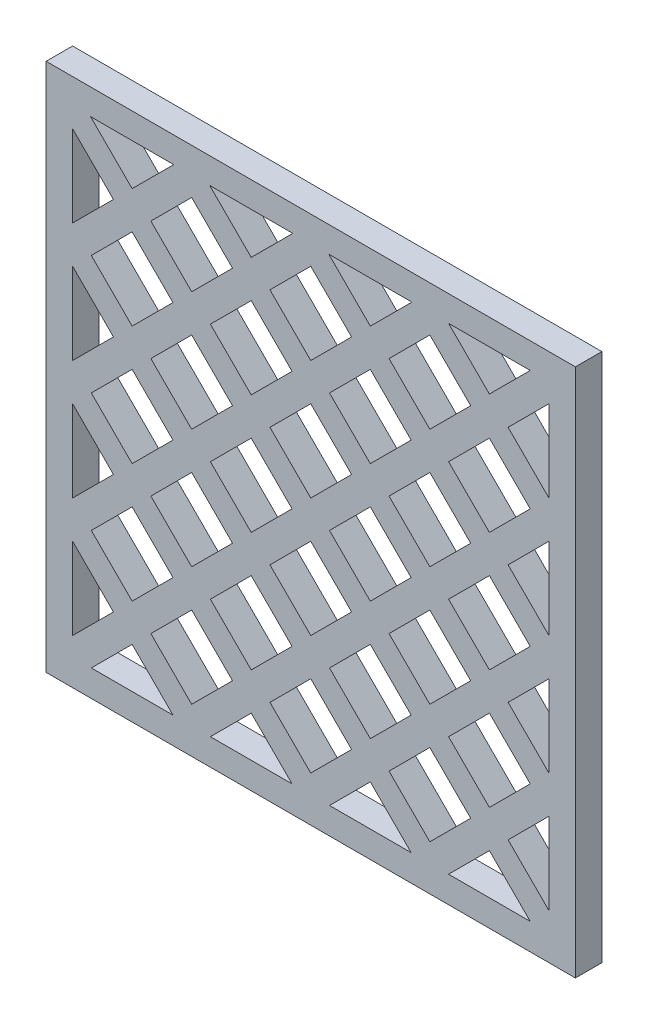
SolidWorks part; units mm, degrees
ref_plane "Front Plane" through (0, 0, 0) normal (0, 0, 1) x (1, 0, 0)
ref_plane "Top Plane" through (0, 0, 0) normal (0, 1, 0) x (1, 0, 0)
ref_plane "Right Plane" through (0, 0, 0) normal (1, 0, 0) x (0, 0, -1)
sketch "Sketch4" plane through (0, 0, 0) normal (0, 0, 1) x (1, 0, 0)
  line L0 (-16.7778, -18) -> (-10.4142, -18) construction
  line L1 (-16.6426, 18.0568) -> (-10.3574, 18.0568)
  line L2 (-18, 16.5858) -> (-18, 10.4142)
  line L3 (-16.7778, -18) -> (-10.4142, -18)
  line L5 (10.4142, -18) -> (16.5858, -18)
  line L6 (-18, -18) -> (0, 0) construction
  line L7 (-9, -18) -> (-9, -9) construction
  line L8 (-9, -9) -> (-18, -9) construction
  line L9 (-18, -10.4142) -> (-18, -16.7778) construction
  line L12 (-10.4142, -9) -> (-13.5, -12.0858)
  line L15 (-9, -10.4142) -> (-12.0858, -13.5)
  line L16 (-10.2222, -9) -> (-16.7778, -18) construction
  line L17 (-18, -16.7778) -> (-9, -10.2222) construction
  line L22 (-13.5, -13.5) -> (-13.5, -18) construction
  line L23 (-13.5, -18) -> (-13.5, -9) construction
  line L24 (-9, -13.5) -> (-18, -13.5) construction
  line L25 (-18, -13.5) -> (-13.5, -13.5) construction
  line L26 (-14.9142, -13.5) -> (-18, -16.5858)
  line L27 (-13.5, -14.9142) -> (-16.5858, -18)
  line L28 (-9, -16.5858) -> (-12.0858, -13.5)
  line L29 (-13.5, -14.9142) -> (-10.4142, -18)
  line L30 (-14.9142, -13.5) -> (-18, -10.4142)
  line L31 (-16.5858, -9) -> (-13.5, -12.0858)
  line L32 (-5.9142, -13.5) -> (-9, -10.4142)
  line L33 (-7.5858, -9) -> (-4.5, -12.0858)
  line L34 (-1.4142, -9) -> (-4.5, -12.0858)
  line L35 (0, -10.4142) -> (-3.0858, -13.5)
  line L36 (0, -16.5858) -> (-3.0858, -13.5)
  line L37 (-4.5, -14.9142) -> (-1.4142, -18)
  line L38 (-4.5, -14.9142) -> (-7.5858, -18)
  line L39 (-5.9142, -13.5) -> (-9, -16.5858)
  line L40 (3.0858, -13.5) -> (0, -10.4142)
  line L41 (1.4142, -9) -> (4.5, -12.0858)
  line L42 (7.5858, -9) -> (4.5, -12.0858)
  line L43 (9, -10.4142) -> (5.9142, -13.5)
  line L44 (9, -16.5858) -> (5.9142, -13.5)
  line L45 (4.5, -14.9142) -> (7.5858, -18)
  line L46 (4.5, -14.9142) -> (1.4142, -18)
  line L47 (3.0858, -13.5) -> (0, -16.5858)
  line L48 (12.0858, -13.5) -> (9, -10.4142)
  line L49 (10.4142, -9) -> (13.5, -12.0858)
  line L50 (16.5858, -9) -> (13.5, -12.0858)
  line L51 (18, -10.4142) -> (14.9142, -13.5)
  line L52 (18, -16.5858) -> (14.9142, -13.5)
  line L53 (13.5, -14.9142) -> (16.5858, -18)
  line L54 (13.5, -14.9142) -> (10.4142, -18)
  line L55 (12.0858, -13.5) -> (9, -16.5858)
  line L56 (-5.9142, -4.5) -> (-9, -1.4142)
  line L57 (-7.5858, 0) -> (-4.5, -3.0858)
  line L58 (-1.4142, 0) -> (-4.5, -3.0858)
  line L59 (0, -1.4142) -> (-3.0858, -4.5)
  line L60 (0, -7.5858) -> (-3.0858, -4.5)
  line L61 (-4.5, -5.9142) -> (-1.4142, -9)
  line L62 (-4.5, -5.9142) -> (-7.5858, -9)
  line L63 (-5.9142, -4.5) -> (-9, -7.5858)
  line L64 (3.0858, -4.5) -> (0, -1.4142)
  line L65 (1.4142, 0) -> (4.5, -3.0858)
  line L66 (7.5858, 0) -> (4.5, -3.0858)
  line L67 (9, -1.4142) -> (5.9142, -4.5)
  line L68 (9, -7.5858) -> (5.9142, -4.5)
  line L69 (4.5, -5.9142) -> (7.5858, -9)
  line L70 (4.5, -5.9142) -> (1.4142, -9)
  line L71 (3.0858, -4.5) -> (0, -7.5858)
  line L72 (12.0858, -4.5) -> (9, -1.4142)
  line L73 (10.4142, 0) -> (13.5, -3.0858)
  line L74 (16.5858, 0) -> (13.5, -3.0858)
  line L75 (18, -1.4142) -> (14.9142, -4.5)
  line L76 (18, -7.5858) -> (14.9142, -4.5)
  line L77 (13.5, -5.9142) -> (16.5858, -9)
  line L78 (13.5, -5.9142) -> (10.4142, -9)
  line L79 (12.0858, -4.5) -> (9, -7.5858)
  line L80 (-5.9142, 4.5) -> (-9, 7.5858)
  line L81 (-7.5858, 9) -> (-4.5, 5.9142)
  line L82 (-1.4142, 9) -> (-4.5, 5.9142)
  line L83 (0, 7.5858) -> (-3.0858, 4.5)
  line L84 (0, 1.4142) -> (-3.0858, 4.5)
  line L85 (-4.5, 3.0858) -> (-1.4142, 0)
  line L86 (-4.5, 3.0858) -> (-7.5858, 0)
  line L87 (-5.9142, 4.5) -> (-9, 1.4142)
  line L88 (3.0858, 4.5) -> (0, 7.5858)
  line L89 (1.4142, 9) -> (4.5, 5.9142)
  line L90 (7.5858, 9) -> (4.5, 5.9142)
  line L91 (9, 7.5858) -> (5.9142, 4.5)
  line L92 (9, 1.4142) -> (5.9142, 4.5)
  line L93 (4.5, 3.0858) -> (7.5858, 0)
  line L94 (4.5, 3.0858) -> (1.4142, 0)
  line L95 (3.0858, 4.5) -> (0, 1.4142)
  line L96 (12.0858, 4.5) -> (9, 7.5858)
  line L97 (10.4142, 9) -> (13.5, 5.9142)
  line L98 (16.5858, 9) -> (13.5, 5.9142)
  line L99 (18, 7.5858) -> (14.9142, 4.5)
  line L100 (18, 1.4142) -> (14.9142, 4.5)
  line L101 (13.5, 3.0858) -> (16.5858, 0)
  line L102 (13.5, 3.0858) -> (10.4142, 0)
  line L103 (12.0858, 4.5) -> (9, 1.4142)
  line L104 (-5.9142, 13.5) -> (-9, 16.5858)
  line L105 (-7.6426, 18.0568) -> (-4.5, 14.9142)
  line L106 (-1.3574, 18.0568) -> (-4.5, 14.9142)
  line L107 (0, 16.5858) -> (-3.0858, 13.5)
  line L108 (0, 10.4142) -> (-3.0858, 13.5)
  line L109 (-4.5, 12.0858) -> (-1.4142, 9)
  line L110 (-4.5, 12.0858) -> (-7.5858, 9)
  line L111 (-5.9142, 13.5) -> (-9, 10.4142)
  line L112 (3.0858, 13.5) -> (0, 16.5858)
  line L113 (1.3574, 18.0568) -> (4.5, 14.9142)
  line L114 (7.6426, 18.0568) -> (4.5, 14.9142)
  line L115 (9, 16.5858) -> (5.9142, 13.5)
  line L116 (9, 10.4142) -> (5.9142, 13.5)
  line L117 (4.5, 12.0858) -> (7.5858, 9)
  line L118 (4.5, 12.0858) -> (1.4142, 9)
  line L119 (3.0858, 13.5) -> (0, 10.4142)
  line L120 (12.0858, 13.5) -> (9, 16.5858)
  line L121 (10.4142, 18.0568) -> (13.5, 14.9711)
  line L122 (16.5858, 18.0568) -> (13.5, 14.9711)
  line L125 (13.5, 12.0858) -> (16.5858, 9)
  line L126 (13.5, 12.0858) -> (10.4142, 9)
  line L127 (12.0858, 13.5) -> (9, 10.4142)
  line L128 (-14.9142, -4.5) -> (-18, -1.4142)
  line L129 (-16.5858, 0) -> (-13.5, -3.0858)
  line L130 (-10.4142, 0) -> (-13.5, -3.0858)
  line L131 (-9, -1.4142) -> (-12.0858, -4.5)
  line L132 (-9, -7.5858) -> (-12.0858, -4.5)
  line L133 (-13.5, -5.9142) -> (-10.4142, -9)
  line L134 (-13.5, -5.9142) -> (-16.5858, -9)
  line L135 (-14.9142, -4.5) -> (-18, -7.5858)
  line L136 (-14.9142, 4.5) -> (-18, 7.5858)
  line L137 (-16.5858, 9) -> (-13.5, 5.9142)
  line L138 (-10.4142, 9) -> (-13.5, 5.9142)
  line L139 (-9, 7.5858) -> (-12.0858, 4.5)
  line L140 (-9, 1.4142) -> (-12.0858, 4.5)
  line L141 (-13.5, 3.0858) -> (-10.4142, 0)
  line L142 (-13.5, 3.0858) -> (-16.5858, 0)
  line L143 (-14.9142, 4.5) -> (-18, 1.4142)
  line L144 (-14.9142, 13.5) -> (-18, 16.5858)
  line L145 (-16.6426, 18.0568) -> (-13.5, 14.9142)
  line L146 (-10.3574, 18.0568) -> (-13.5, 14.9142)
  line L147 (-9, 16.5858) -> (-12.0858, 13.5)
  line L148 (-9, 10.4142) -> (-12.0858, 13.5)
  line L149 (-13.5, 12.0858) -> (-10.4142, 9)
  line L150 (-13.5, 12.0858) -> (-16.5858, 9)
  line L151 (-14.9142, 13.5) -> (-18, 10.4142)
  line L152 (-18, 10.4142) -> (-18, 16.5858)
  line L153 (-16.6426, 18.0568) -> (-10.3574, 18.0568)
  line L154 (-7.6426, 18.0568) -> (-1.3574, 18.0568)
  line L155 (1.3574, 18.0568) -> (7.6426, 18.0568)
  line L156 (10.4142, 18.0568) -> (16.5858, 18.0568)
  line L158 (18, 7.5858) -> (18, 1.4142)
  line L159 (18, -1.4142) -> (18, -7.5858)
  line L160 (18, -10.4142) -> (18, -16.5858)
  line L161 (0, 0) -> (16.5858, 0) construction
  line L162 (10.4142, -18) -> (16.5858, -18)
  line L163 (7.5858, -18) -> (1.4142, -18)
  line L164 (-1.4142, -18) -> (-7.5858, -18)
  line L165 (-10.4142, -18) -> (-16.7778, -18)
  line L166 (-18, -16.5858) -> (-18, -10.4142)
  line L167 (-16.5858, -18) -> (-10.4142, -18)
  line L168 (-18, -7.5858) -> (-18, -1.4142)
  line L169 (-18, 1.4142) -> (-18, 7.5858)
  line L170 (-18, 7.5858) -> (-18, 1.4142)
  line L171 (-7.6426, 18.0568) -> (-1.3574, 18.0568)
  line L172 (1.3574, 18.0568) -> (7.6426, 18.0568)
  line L173 (10.4142, 18.0568) -> (16.5858, 18.0568)
  line L174 (18, 7.5858) -> (18, 1.4142)
  line L175 (18, -10.4142) -> (18, -16.5858)
  line L176 (1.4142, -18) -> (7.5858, -18)
  line L177 (-7.5858, -18) -> (-1.4142, -18)
  line L178 (-18, -10.4142) -> (-18, -16.7778)
  line L179 (-18, -1.4142) -> (-18, -7.5858)
  line L180 (18, 16.5858) -> (18, 10.4142)
  line L181 (18, 10.4142) -> (14.9142, 13.5)
  line L182 (18, 16.5858) -> (14.9142, 13.5)
  point P0 (0, 0)
  dimension "D1" = 4.364
  dimension "D2" = 2
  dimension "D3" = 1
  dimension "D4" = 6.1716
  dimension "D5" = 1
sketch "Sketch5" plane through (0, 0, 0) normal (0, 0, 1) x (1, 0, 0)
  line L1 (-20, 20) -> (20, 20)
  line L2 (-20, 20) -> (-20, -20)
  line L3 (-20, -20) -> (20, -20)
  line L4 (20, 20) -> (20, -20)
  line L5 (-20, 20) -> (20, -20) construction
  line L6 (-20, -20) -> (20, 20) construction
  point P0 (0, 0)
  dimension "D1" = 40
  dimension "D2" = 40
extrude "Boss-Extrude2" add sketch "Sketch5" along normal blind 2
extrude "Cut-Extrude1" cut sketch "Sketch4" along normal blind 2 contours L180 L182 L181 | L156 L121 L122 region at (13.5, 17.0283, 0) region at (16.9714, 13.5, 0)
extrude "Cut-Extrude4" cut sketch "Sketch4<5>" along normal blind 2 contours L29 L27 L3 | L39 L32 L15 L28 | L133 L134 L31 L12 | L166 L26 L30 region at (-13.5, -16.9714, 0) region at (-13.5, -9, 0) region at (-9, -13.5, 0) region at (-16.9714, -13.5, 0)
sketch "Sketch4<5>" plane through (0, 0, 0) normal (0, 0, 1) x (1, 0, 0) same geometry as "Sketch4"
extrude "Cut-Extrude5" cut sketch "Sketch4<6>" along normal blind 2 contours L164 L37 L38 | L47 L40 L35 L36 | L163 L45 L46 | L55 L48 L43 L44 | L53 L54 L5 | L160 L51 L52 | L77 L78 L49 L50 | L69 L70 L41 L42 | L79 L72 L67 L68 | L159 L75 L76 region at (13.5, -16.9714, 0) region at (0, -13.5, 0) region at (-4.5, -16.9714, 0) region at (4.5, -9, 0) region at (9, -13.5, 0) region at (4.5, -16.9714, 0) region at (13.5, -9, 0) region at (16.9714, -13.5, 0) region at (9, -4.5, 0) region at (16.9714, -4.5, 0)
sketch "Sketch4<6>" plane through (0, 0, 0) normal (0, 0, 1) x (1, 0, 0) same geometry as "Sketch4"
extrude "Cut-Extrude6" cut sketch "Sketch4<7>" along normal blind 2 contours L101 L102 L73 L74 | L158 L99 L100 | L125 L126 L97 L98 | L103 L96 L91 L92 | L117 L118 L89 L90 | L127 L120 L115 L116 | L155 L113 L114 | L119 L112 L107 L108 | L95 L88 L83 L84 | L93 L94 L65 L66 | L71 L64 L59 L60 | L61 L62 L33 L34 region at (-4.5, -9, 0) region at (0, -4.5, 0) region at (4.5, 0, 0) region at (13.5, 0, 0) region at (0, 4.5, 0) region at (4.5, 9, 0) region at (9, 4.5, 0) region at (13.5, 9, 0) region at (16.9714, 4.5, 0) region at (0, 13.5, 0) region at (4.5, 17.0093, 0) region at (9, 13.5, 0)
sketch "Sketch4<7>" plane through (0, 0, 0) normal (0, 0, 1) x (1, 0, 0) same geometry as "Sketch4"
extrude "Cut-Extrude7" cut sketch "Sketch4<9>" along normal blind 2 contours L140 L87 L80 L139 | L85 L86 L57 L58 | L132 L63 L56 L131 | L141 L142 L129 L130 | L168 L135 L128 | L169 L143 L136 region at (-9, -4.5, 0) region at (-4.5, 0, 0) region at (-9, 4.5, 0) region at (-16.9714, -4.5, 0) region at (-13.5, 0, 0) region at (-16.9714, 4.5, 0)
sketch "Sketch4<9>" plane through (0, 0, 0) normal (0, 0, 1) x (1, 0, 0) same geometry as "Sketch4"
extrude "Cut-Extrude8" cut sketch "Sketch4<10>" along normal blind 2 contours L109 L110 L81 L82 | L148 L111 L104 L147 | L149 L150 L137 L138 | L151 L144 L2 | L146 L1 L145 | L154 L105 L106 region at (-13.5, 17.0093, 0) region at (-16.9714, 13.5, 0) region at (-4.5, 9, 0) region at (-9, 13.5, 0) region at (-4.5, 17.0093, 0) region at (-13.5, 9, 0)
sketch "Sketch4<10>" plane through (0, 0, 0) normal (0, 0, 1) x (1, 0, 0) same geometry as "Sketch4"
